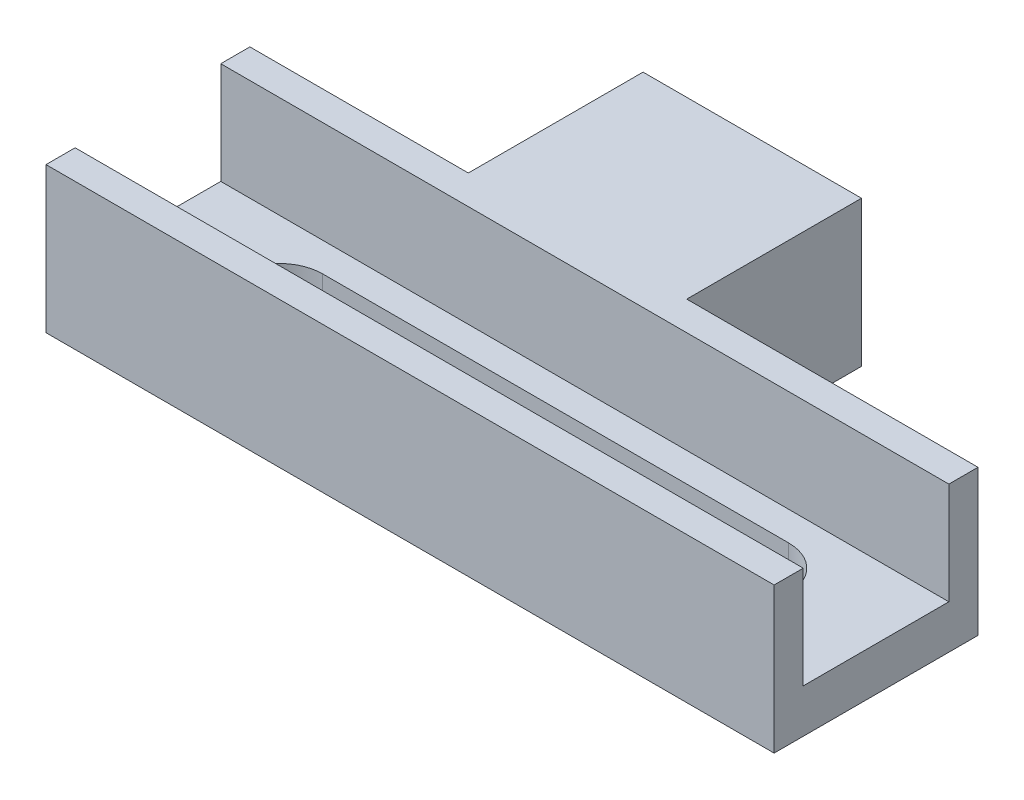
SolidWorks part; units mm, degrees
ref_plane "Front Plane" through (0, 0, 0) normal (0, 0, 1) x (1, 0, 0)
ref_plane "Top Plane" through (0, 0, 0) normal (0, 1, 0) x (1, 0, 0)
ref_plane "Right Plane" through (0, 0, 0) normal (1, 0, 0) x (0, 0, -1)
sketch "Sketch1" plane through (0, 0, 0) normal (0, 1, 0) x (1, 0, 0)
  line L1 (0, 0) -> (-50, 0)
  line L2 (0, 0) -> (0, 26)
  line L3 (0, 26) -> (-50, 26)
  line L4 (-50, 0) -> (-50, 26)
  dimension "D1" = 50
  dimension "D2" = 26
extrude "Boss-Extrude1" add sketch "Sketch1" along normal blind 10
sketch "Sketch2" plane through (0, 10, 0) normal (0, 1, 0) x (1, 0, 0)
  line L1 (-50, 26) -> (-35, 26)
  line L2 (-50, 26) -> (-50, 14)
  line L3 (-50, 14) -> (-35, 14)
  line L4 (-35, 26) -> (-35, 14)
  line L5 (0, 26) -> (-20, 26)
  line L6 (0, 26) -> (0, 14)
  line L7 (0, 14) -> (-20, 14)
  line L8 (-20, 26) -> (-20, 14)
  dimension "D1" = 12
  dimension "D2" = 12
  dimension "D3" = 15
  dimension "D4" = 15
extrude "Cut-Extrude1" cut sketch "Sketch2" against normal through all
sketch "Sketch3" plane through (-50, 0, 0) normal (-1, 0, 0) x (0, 0, 1)
  line L0 (-14, 10) -> (0, 10) construction
  line L1 (-12, 10) -> (-2, 10)
  line L2 (-12, 10) -> (-12, 3)
  line L3 (-12, 3) -> (-2, 3)
  line L4 (-2, 10) -> (-2, 3)
  line L5 (-14, 0) -> (-14, 10) construction
  line L6 (0, 10) -> (0, 0) construction
  dimension "D1" = 2
  dimension "D2" = 2
  dimension "D3" = 7
extrude "Cut-Extrude2" cut sketch "Sketch3" against normal through all
sketch "Sketch4" plane through (0, 3, 0) normal (0, 1, 0) x (1, 0, 0)
  line L0 (-41, 10) -> (-9, 10)
  line L2 (-41, 4) -> (-9, 4)
  line L6 (0, 12) -> (-50, 12) construction
  arc A0 (-41, 4) -> (-41, 10) centre (-41, 7) cw
  arc A1 (-9, 10) -> (-9, 4) centre (-9, 7) cw
  point P10 (-6, 7)
  dimension "D5" = 3
  dimension "D1" = 6
  dimension "D4" = 2
extrude "Cut-Extrude3" cut sketch "Sketch4" against normal through all
sketch "Sketch6" plane through (0, 0, -26) normal (0, 0, -1) x (-1, 0, 0)
  line L0 (20, 0) -> (35, 0) construction
  line L1 (20, 0) -> (20, 10) construction
  circle A0 centre (25, 5) radius 2.5
  dimension "D1" = 5
  dimension "D2" = 5
  dimension "D3" = 5
extrude "Cut-Extrude4" cut sketch "Sketch6" against normal blind 10
sketch "Sketch7" plane through (-35, 0, 0) normal (-1, 0, 0) x (0, 0, 1)
  line L0 (-14, 10) -> (-26, 10) construction
  line L1 (-26, 0) -> (-26, 10) construction
  circle A0 centre (-21, 5) radius 2.5
  dimension "D1" = 5
  dimension "D3" = 5
  dimension "D2" = 5
extrude "Cut-Extrude5" cut sketch "Sketch7" against normal blind 10
chamfer "Chamfer1" distance 0.25 angle 45 1 edges at (-35, 5, -18.5)
thread "Thread1" pitch 0.8 method extrude profile "Thread Profile1" start angle 0, offset 0, length 6.5, pitch 0.8, diameter 5
ref_plane "Plane1" through (-34.75, 5, -23.5) normal (0, -1, 0) x (0, 0, -1)
sketch "Thread Profile1" plane through (-34.75, 5, -23.5) normal (0, -1, 0) x (0, 0, -1)
  line L0 (0, 0) -> (0, 0.8) construction
  line L11 (0, 0) -> (0, 0.7)
  line L12 (0, 0.7) -> (-0.433, 0.45)
  line L13 (-0.433, 0.45) -> (-0.433, 0.25)
  line L15 (-0.433, 0.25) -> (0, 0)
  line L17 (-0.433, 0.35) -> (0, 0.35) construction
  point P2 (0, 0)
  dimension "Pitch" = 0.8
  dimension "Profile_Angle" = 60
  dimension "Profile_Land" = 0.2
  dimension "Profile_Height" = 0.433
